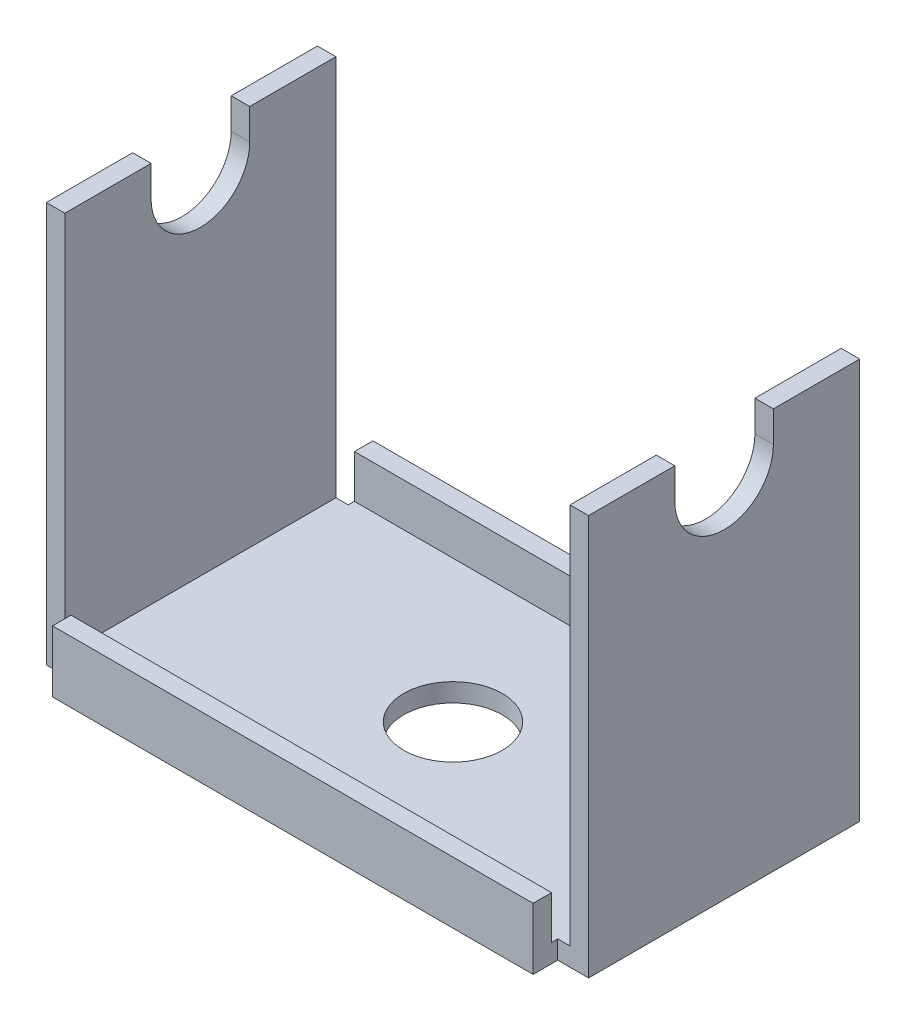
SolidWorks part; units mm, degrees
ref_plane "Front Plane" through (0, 0, 0) normal (0, 0, 1) x (1, 0, 0)
ref_plane "Top Plane" through (0, 0, 0) normal (0, 1, 0) x (1, 0, 0)
ref_plane "Right Plane" through (0, 0, 0) normal (1, 0, 0) x (0, 0, -1)
sketch "Sketch1" plane through (0, 0, 0) normal (0, 0, 1) x (1, 0, 0)
  line L0 (-22, 2.5) -> (-22, -30)
  line L1 (-22, -30) -> (22, -30)
  line L2 (22, -30) -> (22, 2.5)
  line L3 (22, 2.5) -> (20.5, 2.5)
  line L4 (20.5, 2.5) -> (20.5, -28.5)
  line L5 (20.5, -28.5) -> (-20.5, -28.5)
  line L6 (-20.5, -28.5) -> (-20.5, 2.5)
  line L7 (-20.5, 2.5) -> (-22, 2.5)
  dimension "D1" = 1.5
  dimension "D2" = 1.5
  dimension "D3" = 32.5
  dimension "D4" = 44
  dimension "D5" = 30
  dimension "D6" = 22
extrude "Boss-Extrude1" add sketch "Sketch1" against normal mid plane 22
sketch "Sketch2" plane through (0, 0, 0) normal (1, 0, 0) x (0, 0, -1)
  line L0 (-11, -30) -> (-13, -30)
  line L1 (-13, -30) -> (-13, -25)
  line L2 (-13, -25) -> (-11.5, -25)
  line L3 (-11.5, -25) -> (-11.5, -28.5)
  line L4 (-11.5, -28.5) -> (-11, -28.5)
  line L5 (-11, -30) -> (-11, 2.5) construction
  line L6 (-11, -28.5) -> (-11, -30)
  dimension "D1" = 1.5
  dimension "D2" = 0.5
  dimension "D3" = 5
extrude "Boss-Extrude2" add sketch "Sketch2" along normal mid plane 39
mirror "Mirror1" about plane through (0, 0, 0) normal (0, 0, 1) of "Boss-Extrude2"
sketch "Sketch3" plane through (0, -28.5, 0) normal (0, 1, 0) x (-1, 0, 0)
  line L0 (0, 0) -> (0, -11.5) construction
  line L1 (-19.5, -11.5) -> (19.5, -11.5) construction
  line L2 (0, 0) -> (-20.5, 0) construction
  line L3 (-20.5, -11) -> (-20.5, 11) construction
  circle A0 centre (0, 0) radius 4
  dimension "D1" = 8
extrude "Cut-Extrude1" cut sketch "Sketch3" against normal through all
sketch "Sketch4" plane through (22, 0, 0) normal (1, 0, 0) x (0, 0, -1)
  line L0 (0, 0) -> (0, 2.5) construction
  line L1 (11, 2.5) -> (-11, 2.5) construction
  line L2 (11, -30) -> (-11, -30) construction
  line L3 (-4, 0) -> (-4, 2.5)
  line L4 (-4, 2.5) -> (4, 2.5)
  line L5 (4, 2.5) -> (4, 0)
  arc A0 (-4, 0) -> (4, 0) centre (0, 0) ccw
  dimension "D2" = 4
  dimension "D1" = 30
extrude "Cut-Extrude2" cut sketch "Sketch4" against normal through all
